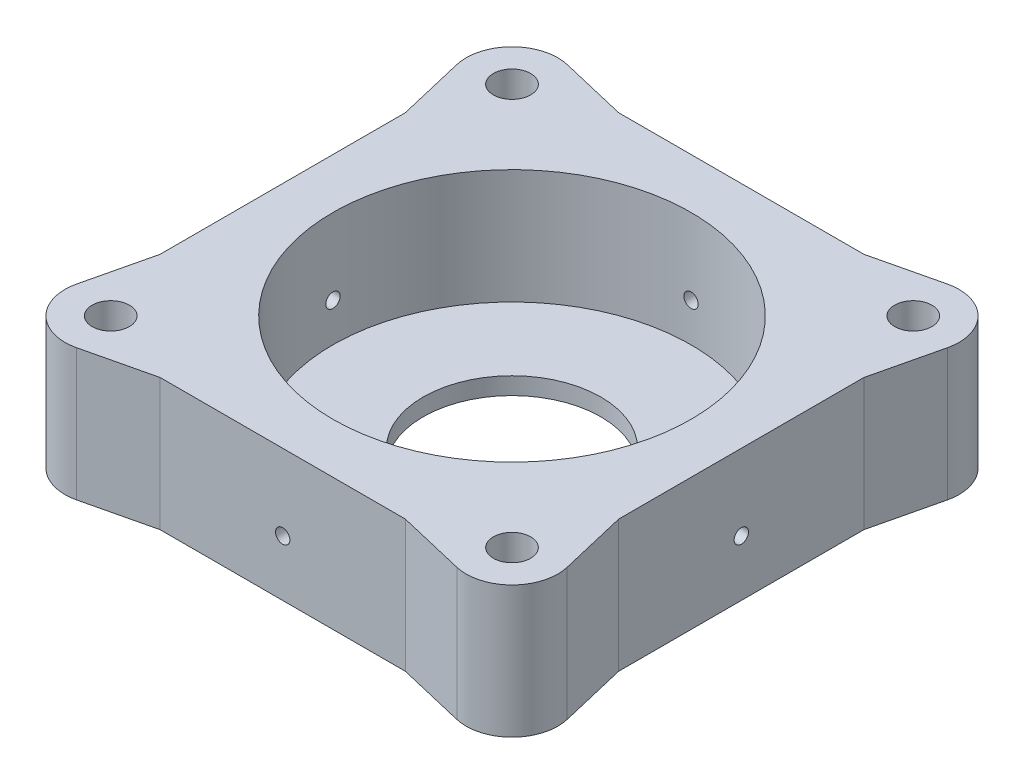
SolidWorks part; units mm, degrees
ref_plane "Front Plane" through (0, 0, 0) normal (0, 0, 1) x (1, 0, 0)
ref_plane "Top Plane" through (0, 0, 0) normal (0, 1, 0) x (1, 0, 0)
ref_plane "Right Plane" through (0, 0, 0) normal (1, 0, 0) x (0, 0, -1)
sketch "Sketch1" plane through (0, 0, 0) normal (0, 1, 0) x (1, 0, 0)
  line L0 (0, 35) -> (0, -35) construction
  line L1 (35, -35) -> (-35, -35)
  line L2 (35, -35) -> (35, 35)
  line L3 (35, 35) -> (-35, 35)
  line L4 (-35, -35) -> (-35, 35)
  line L5 (35, -35) -> (-35, 35) construction
  line L6 (35, 35) -> (-35, -35) construction
  line L7 (-35, 0) -> (35, 0) construction
  line L8 (-33.1578, 42.785) -> (7.8292, 33.0863)
  line L9 (-42.785, 33.1578) -> (-33.0863, -7.8292)
  line L10 (42.785, 33.1578) -> (33.0863, -7.8292)
  line L11 (33.1578, 42.785) -> (-7.8292, 33.0863)
  line L12 (-42.785, -33.1578) -> (-33.0863, 7.8292)
  line L13 (-33.1578, -42.785) -> (7.8292, -33.0863)
  line L14 (33.1578, -42.785) -> (-7.8292, -33.0863)
  line L15 (42.785, -33.1578) -> (33.0863, 7.8292)
  line L17 (40, -40) -> (-40, -40)
  line L18 (40, -40) -> (40, 40)
  line L19 (40, 40) -> (-40, 40)
  line L20 (-40, -40) -> (-40, 40)
  line L21 (40, -40) -> (-40, 40) construction
  line L22 (40, 40) -> (-40, -40) construction
  circle A0 centre (0, 0) radius 15.5
  circle A1 centre (0, 0) radius 34
  circle A2 centre (-35, 35) radius 3.25
  circle A3 centre (0, 0) radius 40
  circle A4 centre (-35, 35) radius 8
  circle A5 centre (35, 35) radius 3.25
  circle A6 centre (35, 35) radius 8
  circle A7 centre (-35, -35) radius 3.25
  circle A8 centre (-35, -35) radius 8
  circle A9 centre (35, -35) radius 3.25
  circle A10 centre (35, -35) radius 8
  dimension "D1" = 31
  dimension "D2" = 68
  dimension "D3" = 6.5
  dimension "D5" = 80
  dimension "D4" = 16
  dimension "D6" = 70
extrude "Boss-Extrude1" add sketch "Sketch1" along normal blind 19.5 contours L19 A4 L20 | L3 A4 L19 L20 L4 A2 | L4 A4 L3 A2 | A4 L9 L20 | A4 L20 L9 A3 L4 | A3 L9 L20 | L4 A3 L9 | L9 A3 L12 L4 | A3 L20 L12 | L12 A3 L4 | L20 A8 L4 A3 L12 | L12 A8 L20 | A8 L17 L20 | A8 L20 L17 L1 A7 L4 | A8 L4 A7 L1 | L4 A8 L1 A3 | L4 A3 L1 L13 L14 A1 L9 L12 | L3 A3 L4 L9 L12 A1 L11 L8 | A1 L12 L9 | A4 L4 A3 L3 | A4 L3 A3 L8 L19 | A4 L19 L8 | A3 L19 L8 | L8 A3 L3 | L11 A3 L8 L3 | A1 L8 L11 | L3 A3 L11 | L2 A3 L3 L11 L8 A1 L15 L10 | L3 A6 L19 L11 A3 | A3 L11 L19 | L19 A6 L11 | L2 A6 L3 A3 | A6 L2 A5 L3 | A6 L3 A5 L2 L18 L19 | A6 L19 L18 | L10 A6 L18 | L18 A6 L2 A3 L10 | A3 L18 L10 | L10 A3 L2 | L15 A3 L10 L2 | A3 L15 L18 | L2 A3 L15 | A1 L10 L15 | L1 A3 L2 L15 L10 A1 L13 L14 | A10 L18 L15 A3 L2 | A10 L15 L18 | A10 L2 A3 L1 | L18 A10 L2 A9 L1 L17 | L2 A10 L1 A9 | A10 L18 L17 | A10 L17 L14 | A10 L1 A3 L14 L17 | L14 A3 L1 | A3 L17 L14 | A3 L14 L1 L13 | A1 L14 L13 | L1 A3 L13 | A3 L13 L17 | L1 A8 L17 L13 A3 | L17 A8 L13 | A1 A0 region at (-27.625, 0, 37.5886) region at (-28.9419, 0, 28.9419) region at (-31.2062, 0, 31.2062) region at (-21.8672, 0, 37.555) region at (-24.6184, 0, 24.6184) region at (-10.9152, 0, 35.995) region at (-37.555, 0, 21.8672) region at (-30.8311, 0, 41.5907) region at (-27.2274, 0, 40.8217) region at (0, 0, 37.8149) region at (-35.995, 0, 10.9152) region at (-12.614, 0, 39.3478) region at (-40.8217, 0, 27.2274) region at (24.6184, 0, 24.6184) region at (10.9152, 0, 35.995) region at (0, 0, 34.191) region at (-37.8149, 0, 0) region at (-39.3478, 0, 12.614) region at (12.614, 0, 39.3478) region at (28.9419, 0, 28.9419) region at (21.8672, 0, 37.555) region at (0, 0, 33.0383) region at (-35.995, 0, -10.9152) region at (-24.6184, 0, -24.6184) region at (-34.191, 0, 0) region at (-39.3478, 0, -12.614) region at (27.2274, 0, 40.8217) region at (31.2062, 0, 31.2062) region at (29.375, 0, 35.1838) region at (37.555, 0, 21.8672) region at (35.995, 0, 10.9152) region at (34.191, 0, 0) region at (-37.555, 0, -21.8672) region at (-28.9419, 0, -28.9419) region at (-40.8217, 0, -27.2274) region at (30.8311, 0, 41.5907) region at (37.8149, 0, 0) region at (39.3478, 0, 12.614) region at (24.6184, 0, -24.6184) region at (-37.5886, 0, -27.625) region at (-31.2062, 0, -31.2062) region at (-10.9152, 0, -35.995) region at (-21.8672, 0, -37.555) region at (0, 0, -34.191) region at (-40.5144, 0, -40.5144) region at (40.8217, 0, 27.2274) region at (35.995, 0, -10.9152) region at (39.3478, 0, -12.614) region at (0, 0, -37.8149) region at (-12.614, 0, -39.3478) region at (-27.2274, 0, -40.8217) region at (28.9419, 0, -28.9419) region at (37.555, 0, -21.8672) region at (40.8217, 0, -27.2274) region at (10.9152, 0, -35.995) region at (12.614, 0, -39.3478) region at (31.2062, 0, -31.2062) region at (35.1838, 0, -29.375) region at (21.8672, 0, -37.555) region at (41.5907, 0, -30.8311)
sketch "Sketch2" plane through (0, 19.5, 0) normal (0, 1, 0) x (1, 0, 0)
  circle A0 centre (0, 0) radius 31.25
  dimension "D1" = 62.5
extrude "Cut-Extrude1" cut sketch "Sketch2" against normal blind 16.5
sketch "Sketch3" plane through (0, 0, 0) normal (0, -1, 0) x (1, 0, 0)
  circle A0 centre (-35, 35) radius 5
  circle A1 centre (35, 35) radius 5
  circle A2 centre (35, -35) radius 5
  circle A3 centre (-35, -35) radius 5
  dimension "D1" = 10
extrude "Cut-Extrude2" cut sketch "Sketch3" against normal blind 6
sketch "Sketch4" plane through (0, 0, 40) normal (0, 0, 1) x (1, 0, 0)
  line L0 (0, 0) -> (0, 19.5) construction
  line L1 (21.3883, 0) -> (-21.3883, 0) construction
  line L2 (21.3883, 19.5) -> (-21.3883, 19.5) construction
  circle A0 centre (0, 9.75) radius 1.25
  dimension "D1" = 2.5
extrude "Cut-Extrude3" cut sketch "Sketch4" against normal up to surface (80 mm away) up to face at (0, 9.75, -40)
sketch "Sketch5" plane through (40, 0, 0) normal (1, 0, 0) x (0, 0, -1)
  line L0 (0, 0) -> (0, 19.5) construction
  line L1 (-21.3883, 19.5) -> (21.3883, 19.5) construction
  circle A0 centre (0, 9.75) radius 1.25
  dimension "D1" = 2.5
extrude "Cut-Extrude4" cut sketch "Sketch5" against normal up to surface (80 mm away) up to face at (-40, 9.75, 0)
sketch "Sketch6" plane through (0, 19.5, 0) normal (0, 1, 0) x (1, 0, 0)
  line L12 (21.3883, -40) -> (33.1578, -42.785)
  line L13 (42.785, -33.1578) -> (40, -21.3883)
  line L14 (40, -21.3883) -> (40, 21.3883)
  line L15 (40, 21.3883) -> (42.785, 33.1578)
  line L16 (33.1578, 42.785) -> (21.3883, 40)
  line L17 (21.3883, 40) -> (-21.3883, 40)
  line L18 (-21.3883, 40) -> (-33.1578, 42.785)
  line L19 (-42.785, 33.1578) -> (-40, 21.3883)
  line L20 (-40, 21.3883) -> (-40, -21.3883)
  line L21 (-40, -21.3883) -> (-42.785, -33.1578)
  line L22 (-33.1578, -42.785) -> (-21.3883, -40)
  line L23 (-21.3883, -40) -> (21.3883, -40)
  line L24 (21.3883, -40) -> (33.1578, -42.785)
  line L25 (42.785, -33.1578) -> (40, -21.3883)
  line L26 (40, -21.3883) -> (40, 21.3883)
  line L27 (40, 21.3883) -> (42.785, 33.1578)
  line L28 (33.1578, 42.785) -> (21.3883, 40)
  line L29 (21.3883, 40) -> (-21.3883, 40)
  line L30 (-21.3883, 40) -> (-33.1578, 42.785)
  line L31 (-42.785, 33.1578) -> (-40, 21.3883)
  line L32 (-40, 21.3883) -> (-40, -21.3883)
  line L33 (-40, -21.3883) -> (-42.785, -33.1578)
  line L34 (-33.1578, -42.785) -> (-21.3883, -40)
  line L35 (-21.3883, -40) -> (21.3883, -40)
  circle A0 centre (0, 0) radius 31.25 construction
  circle A1 centre (35, 35) radius 3.25 construction
  circle A2 centre (-35, 35) radius 3.25 construction
  circle A3 centre (35, -35) radius 3.25 construction
  arc A4 (33.1578, -42.785) -> (42.785, -33.1578) centre (35, -35) ccw
  arc A5 (42.785, 33.1578) -> (33.1578, 42.785) centre (35, 35) ccw
  arc A6 (-33.1578, 42.785) -> (-42.785, 33.1578) centre (-35, 35) ccw
  arc A7 (-42.785, -33.1578) -> (-33.1578, -42.785) centre (-35, -35) ccw
  arc A8 (33.1578, -42.785) -> (42.785, -33.1578) centre (35, -35) ccw
  arc A9 (42.785, 33.1578) -> (33.1578, 42.785) centre (35, 35) ccw
  arc A10 (-33.1578, 42.785) -> (-42.785, 33.1578) centre (-35, 35) ccw
  arc A11 (-42.785, -33.1578) -> (-33.1578, -42.785) centre (-35, -35) ccw
  circle A12 centre (-35, -35) radius 3.25 construction
  circle A13 centre (0, 0) radius 31.25
  circle A14 centre (35, 35) radius 3.25
  circle A15 centre (-35, 35) radius 3.25
  circle A16 centre (35, -35) radius 3.25
  circle A17 centre (-35, -35) radius 3.25
  dimension "D1" = 0
extrude "Boss-Extrude4" add sketch "Sketch6" along normal blind 3.5
sketch "Sketch7" plane through (0, 0, 0) normal (0, -1, 0) x (1, 0, 0)
  line L0 (-35, 35) -> (-38.7123, 38.7123) construction
  line L1 (-29.1444, 33.431) -> (-30.7134, 39.2866)
  line L2 (-30.7134, 39.2866) -> (-36.569, 40.8556)
  line L3 (-36.569, 40.8556) -> (-40.8556, 36.569)
  line L4 (-40.8556, 36.569) -> (-39.2866, 30.7134)
  line L5 (-39.2866, 30.7134) -> (-33.431, 29.1444)
  line L6 (-33.431, 29.1444) -> (-29.1444, 33.431)
  line L7 (39.2866, 30.7134) -> (40.8556, 36.569)
  line L8 (40.8556, 36.569) -> (36.569, 40.8556)
  line L9 (36.569, 40.8556) -> (30.7134, 39.2866)
  line L10 (30.7134, 39.2866) -> (29.1444, 33.431)
  line L11 (29.1444, 33.431) -> (33.431, 29.1444)
  line L12 (33.431, 29.1444) -> (39.2866, 30.7134)
  line L13 (30.7134, -39.2866) -> (36.569, -40.8556)
  line L14 (36.569, -40.8556) -> (40.8556, -36.569)
  line L15 (40.8556, -36.569) -> (39.2866, -30.7134)
  line L16 (39.2866, -30.7134) -> (33.431, -29.1444)
  line L17 (33.431, -29.1444) -> (29.1444, -33.431)
  line L18 (29.1444, -33.431) -> (30.7134, -39.2866)
  line L19 (-39.2866, -30.7134) -> (-40.8556, -36.569)
  line L20 (-40.8556, -36.569) -> (-36.569, -40.8556)
  line L21 (-36.569, -40.8556) -> (-30.7134, -39.2866)
  line L22 (-30.7134, -39.2866) -> (-29.1444, -33.431)
  line L23 (-29.1444, -33.431) -> (-33.431, -29.1444)
  line L24 (-33.431, -29.1444) -> (-39.2866, -30.7134)
  line L25 (0, 40) -> (0, -40) construction
  line L26 (21.3883, 40) -> (-21.3883, 40) construction
  line L27 (21.3883, -40) -> (-21.3883, -40) construction
  circle A0 centre (-35, 35) radius 5.25 construction
  point P32 (0, 0)
  dimension "D1" = 10.5
  dimension "D2" = 4
extrude "Cut-Extrude5" cut sketch "Sketch7" against normal blind 7.7
